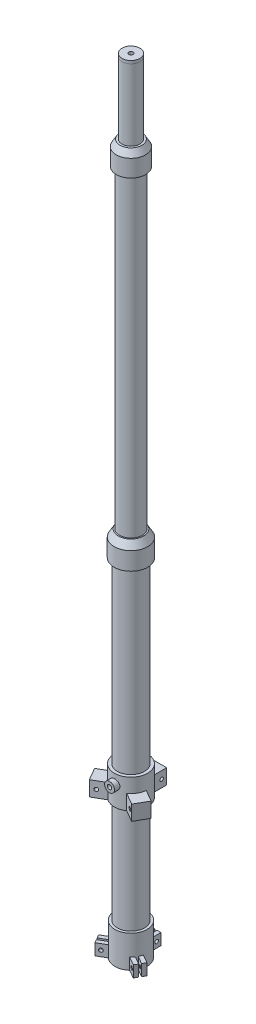
SolidWorks part; units mm, degrees
material "6063-T6"
ref_plane "Спереди" through (0, 0, 0) normal (0, 0, 1) x (1, 0, 0)
ref_plane "Сверху" through (0, 0, 0) normal (0, 1, 0) x (1, 0, 0)
ref_plane "Справа" through (0, 0, 0) normal (1, 0, 0) x (0, 0, -1)
sketch "Эскиз1" plane through (0, 0, 0) normal (0, 1, 0) x (1, 0, 0)
  circle A0 centre (0, 0) radius 20.5
  dimension "D1" = 41
extrude "Бобышка-Вытянуть1" add sketch "Эскиз1" along normal blind 33
chamfer "Фаска1" distance 9 angle 30 1 edges at (0, 33, 20.5) first distance on face at (0, 33, 20.5)
sketch "Эскиз2" plane through (0, 0, 0) normal (0, -1, 0) x (1, 0, 0)
  circle A0 centre (0, 0) radius 16
  dimension "D1" = 32
extrude "--столбик2 (max 440)" add sketch "Эскиз2" along normal blind 440
sketch "Эскиз3" plane through (0, -440, 0) normal (0, -1, 0) x (1, 0, 0)
  circle A0 centre (0, 0) radius 23.5
  dimension "D1" = 47
extrude "Бобышка-Вытянуть3" add sketch "Эскиз3" along normal blind 35
chamfer "Фаска2" distance 10 angle 30 1 edges at (0, -440, -23.5) first distance on face at (0, -475, -23.5)
sketch "Эскиз4" plane through (0, -475, 0) normal (0, -1, 0) x (1, 0, 0)
  circle A0 centre (0, 0) radius 19
  dimension "D1" = 38
extrude "Бобышка-Вытянуть4" add sketch "Эскиз4" along normal blind 485
sketch "Эскиз12" plane through (0, -960, 0) normal (0, -1, 0) x (1, 0, 0)
  circle A0 centre (0, 0) radius 18
  circle A1 centre (0, 0) radius 19 construction
  dimension "D1" = 1
extrude "Вырез-Вытянуть2" cut sketch "Эскиз12" against normal blind 510
sketch "Эскиз14" plane through (0, -450, 0) normal (0, -1, 0) x (1, 0, 0)
  circle A0 centre (0, 0) radius 15.5
  dimension "D1" = 31
extrude "Вырез-Вытянуть3" cut sketch "Эскиз14" against normal offset from surface (481 mm away) 2 up to face at (0, 33, 15.3038)
sketch "Эскиз15" plane through (0, 33, 0) normal (0, 1, 0) x (1, 0, 0)
  circle A0 centre (0, 0) radius 12.5
  dimension "D1" = 25
extrude "--столбик1 (max 500)" add sketch "Эскиз15" along normal blind 100 thin thin type one direction reverse wall 1
sketch "Эскиз16" plane through (0, 33, 0) normal (0, 1, 0) x (1, 0, 0)
  circle A1 centre (0, 0) radius 11.5
  circle A2 centre (0, 0) radius 11.5 construction
extrude "Вырез-Вытянуть4" cut sketch "Эскиз16" against normal blind 5
sketch "Эскиз17" plane through (0, 133, 0) normal (0, 1, 0) x (1, 0, 0)
  circle A0 centre (0, 0) radius 12.5
extrude "Бобышка-Вытянуть9" add sketch "Эскиз17" along normal blind 4 separate body
sketch "Эскиз18" plane through (0, 137, 0) normal (0, 1, 0) x (1, 0, 0)
  circle A0 centre (0, 0) radius 3
  dimension "D1" = 6
extrude "Вырез-Вытянуть5" cut sketch "Эскиз18" against normal blind 4
ref_plane "Плоскость1" through (0, -725, 0) normal (0, -1, 0) x (-1, 0, 0)
sketch "Эскиз5" plane through (0, -725, 0) normal (0, -1, 0) x (-1, 0, 0)
  circle A0 centre (0, 0) radius 23.3
  circle A1 centre (0, 0) radius 18.5
  dimension "D1" = 46.6
  dimension "D2" = 37
extrude "Бобышка-Вытянуть5" add sketch "Эскиз5" along normal blind 41
sketch "Эскиз6" plane through (0, -960, 0) normal (0, -1, 0) x (1, 0, 0)
  circle A0 centre (0, 0) radius 22.5
  dimension "D1" = 45
extrude "Бобышка-Вытянуть6" add sketch "Эскиз6" against normal blind 45
sketch "Эскиз8" plane through (0, 0, 0) normal (0, 0, 1) x (1, 0, 0)
  line L0 (0, 0) -> (0, -738.5) construction
  line L1 (-20.5, 0) -> (20.5, 0) construction
  line L2 (23.3, -725) -> (-23.3, -725) construction
  circle A0 centre (0, -738.5) radius 6.9
  dimension "D1" = 13.8
  dimension "D2" = 13.5
extrude "Бобышка-Вытянуть7" add sketch "Эскиз8" along normal blind 30
sketch "Эскиз9" plane through (0, -766, 0) normal (0, -1, 0) x (1, 0, 0)
  line L0 (0, 0) -> (0, -29.555) construction
  line L1 (-39.641, 11.3397) -> (-29.641, 28.6603)
  line L2 (10, -40) -> (-10, -40)
  line L3 (10, -40) -> (10, -19.11)
  line L4 (10, -19.11) -> (-10, -19.11)
  line L5 (-10, -40) -> (-10, -19.11)
  line L6 (10, -40) -> (-10, -19.11) construction
  line L7 (10, -19.11) -> (-10, -40) construction
  line L8 (-39.641, 11.3397) -> (-21.5498, 0.8948)
  line L9 (-21.5498, 0.8948) -> (-11.5498, 18.2153)
  line L10 (-29.641, 28.6603) -> (-11.5498, 18.2153)
  line L11 (0, 0) -> (-25.5954, 14.7775) construction
  line L12 (-39.641, 11.3397) -> (-11.5498, 18.2153) construction
  line L13 (-21.5498, 0.8948) -> (-29.641, 28.6603) construction
  line L14 (29.641, 28.6603) -> (39.641, 11.3397)
  line L15 (29.641, 28.6603) -> (11.5498, 18.2153)
  line L16 (11.5498, 18.2153) -> (21.5498, 0.8948)
  line L17 (39.641, 11.3397) -> (21.5498, 0.8948)
  line L18 (0, 0) -> (25.5954, 14.7775) construction
  line L19 (29.641, 28.6603) -> (21.5498, 0.8948) construction
  line L20 (11.5498, 18.2153) -> (39.641, 11.3397) construction
  point P19 (0, 0)
  dimension "D1" = 40
  dimension "D3" = 20
  dimension "D2" = 3
extrude "Бобышка-Вытянуть8" add sketch "Эскиз9" against normal blind 21
sketch "Эскиз22" plane through (0, -960, 0) normal (0, -1, 0) x (1, 0, 0)
  line L0 (0, 0) -> (0, -28.2102) construction
  line L2 (7, -35.0369) -> (-7, -35.0369) construction
  line L3 (7, -35.0369) -> (7, -21.3834)
  line L4 (7, -21.3834) -> (-7, -21.3834) construction
  line L5 (-7, -35.0369) -> (-7, -21.3834)
  line L6 (7, -35.0369) -> (-7, -21.3834) construction
  line L7 (7, -21.3834) -> (-7, -35.0369) construction
  line L11 (-1.5, -21.3834) -> (-1.5, -35.0369)
  line L12 (-7, -21.3834) -> (-1.5, -21.3834)
  line L17 (-7, -35.0369) -> (-1.5, -35.0369)
  line L18 (7, -35.0369) -> (1.5, -35.0369)
  line L19 (1.5, -21.3834) -> (1.5, -35.0369)
  line L20 (7, -21.3834) -> (1.5, -21.3834)
  line L21 (-33.8428, 11.4563) -> (-22.0186, 4.6295)
  line L22 (-26.8428, 23.5806) -> (-15.0186, 16.7539)
  line L23 (-17.7686, 11.9907) -> (-29.5928, 18.8175)
  line L24 (-15.0186, 16.7539) -> (-17.7686, 11.9907)
  line L25 (-26.8428, 23.5806) -> (-29.5928, 18.8175)
  line L26 (-33.8428, 11.4563) -> (-31.0928, 16.2194)
  line L27 (-19.2686, 9.3927) -> (-31.0928, 16.2194)
  line L28 (-22.0186, 4.6295) -> (-19.2686, 9.3927)
  line L29 (-33.8428, 11.4563) -> (-26.8428, 23.5806) construction
  line L30 (-22.0186, 4.6295) -> (-15.0186, 16.7539) construction
  line L31 (-33.8428, 11.4563) -> (-15.0186, 16.7539) construction
  line L32 (-22.0186, 4.6295) -> (-26.8428, 23.5806) construction
  line L33 (26.8428, 23.5806) -> (15.0186, 16.7539)
  line L34 (33.8428, 11.4563) -> (22.0186, 4.6295)
  line L35 (19.2686, 9.3927) -> (31.0928, 16.2194)
  line L36 (22.0186, 4.6295) -> (19.2686, 9.3927)
  line L37 (33.8428, 11.4563) -> (31.0928, 16.2194)
  line L38 (26.8428, 23.5806) -> (29.5928, 18.8175)
  line L39 (17.7686, 11.9907) -> (29.5928, 18.8175)
  line L40 (15.0186, 16.7539) -> (17.7686, 11.9907)
  line L41 (26.8428, 23.5806) -> (33.8428, 11.4563) construction
  line L42 (15.0186, 16.7539) -> (22.0186, 4.6295) construction
  line L43 (26.8428, 23.5806) -> (22.0186, 4.6295) construction
  line L44 (15.0186, 16.7539) -> (33.8428, 11.4563) construction
  circle A0 centre (0, 0) radius 22.5 construction
  point P31 (0, 0)
  dimension "D1" = 14
  dimension "D2" = 3
  dimension "D3" = 3
extrude "Бобышка-Вытянуть10" add sketch "Эскиз22" against normal blind 16
sketch "Эскиз10" plane through (0, -745, 0) normal (0, 1, 0) x (1, 0, 0)
  line L0 (0, 0) -> (0, 33.2434) construction
  line L1 (34.7489, -29.2999) -> (42.7489, -15.4435)
  line L2 (8, 44.7434) -> (-8, 44.7434)
  line L3 (12, 40.7434) -> (12, 21.7434)
  line L4 (12, 21.7434) -> (-12, 21.7434) construction
  line L5 (-12, 40.7434) -> (-12, 21.7434)
  line L6 (12, 44.7434) -> (-12, 21.7434) construction
  line L7 (12, 21.7434) -> (-12, 44.7434) construction
  line L8 (29.2848, -30.764) -> (12.8303, -21.264)
  line L9 (41.2848, -9.9794) -> (24.8303, -0.4794)
  line L10 (12.8303, -21.264) -> (24.8303, -0.4794) construction
  line L11 (32.7489, -32.764) -> (24.8303, -0.4794) construction
  line L12 (12.8303, -21.264) -> (44.7489, -11.9794) construction
  line L13 (-42.7489, -15.4435) -> (-34.7489, -29.2999)
  line L14 (-41.2848, -9.9794) -> (-24.8303, -0.4794)
  line L15 (-29.2848, -30.764) -> (-12.8303, -21.264)
  line L16 (-24.8303, -0.4794) -> (-12.8303, -21.264) construction
  line L17 (-44.7489, -11.9794) -> (-12.8303, -21.264) construction
  line L18 (-24.8303, -0.4794) -> (-32.7489, -32.764) construction
  arc A0 (-8, 44.7434) -> (-12, 40.7434) centre (-8, 40.7434) ccw
  arc A1 (8, 44.7434) -> (12, 40.7434) centre (8, 40.7434) cw
  arc A2 (42.7489, -15.4435) -> (41.2848, -9.9794) centre (39.2848, -13.4435) ccw
  arc A3 (34.7489, -29.2999) -> (29.2848, -30.764) centre (31.2848, -27.2999) cw
  arc A4 (-34.7489, -29.2999) -> (-29.2848, -30.764) centre (-31.2848, -27.2999) ccw
  arc A5 (-42.7489, -15.4435) -> (-41.2848, -9.9794) centre (-39.2848, -13.4435) cw
  point P36 (0, 0)
  dimension "D1" = 4
  dimension "D3" = 24
  dimension "D4" = 23
  dimension "D2" = 3
extrude "ноги" [suppressed] add sketch "Эскиз10" against normal blind 470 and the other way blind 10 separate body thin contours L15 A4 L13 A5 L14 | L8 A3 L1 A2 L9 | L3 A1 L2 A0 L5 thin type one direction wall 1
sketch "Эскиз19" plane through (5, 0, 8.6603) normal (0.5, 0, 0.866) x (0.866, 0, -0.5)
  line L0 (-40, -755.5) -> (-33, -755.5) construction
  line L1 (-40, -745) -> (-40, -766) construction
  line L2 (-35.0369, -952) -> (-29.0369, -952) construction
  line L3 (-35.0369, -944) -> (-35.0369, -960) construction
  circle A0 centre (-33, -755.5) radius 2.5
  circle A1 centre (-29.0369, -952) radius 2.5
  dimension "D2" = 5
  dimension "D4" = 5
  dimension "D1" = 7
  dimension "D3" = 6
extrude "Вырез-Вытянуть6" cut sketch "Эскиз19" against normal blind 30
pattern_circular "Круговой массив3" count 3 over 360 about axis through (0, -960, 0) along (0, 1, 0) of "Вырез-Вытянуть6" reverse direction yes
sketch "Эскиз21" plane through (0, 0, 30) normal (0, 0, 1) x (1, 0, 0)
  circle A0 centre (0, -738.5) radius 3
  dimension "D1" = 6
extrude "Вырез-Вытянуть7" cut sketch "Эскиз21" against normal blind 10
